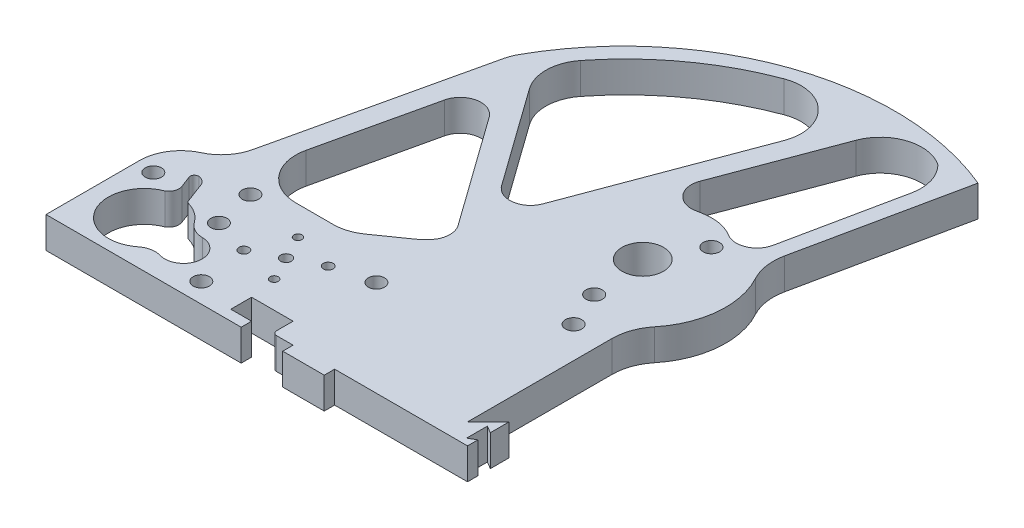
SolidWorks part; units mm, degrees
ref_plane "Front Plane" through (0, 0, 0) normal (0, 0, 1) x (1, 0, 0)
ref_plane "Top Plane" through (0, 0, 0) normal (0, 1, 0) x (1, 0, 0)
ref_plane "Right Plane" through (0, 0, 0) normal (1, 0, 0) x (0, 0, -1)
other "Bounding Box"
ref_plane "Default Plane" through (-8.9266, -12.7485, 0) normal (-0.1736, 0.9848, 0) x (0.9848, 0.1736, 0)
sketch "Sketch1" plane through (0, 0, 0) normal (0, 1, 0) x (1, 0, 0)
  line L0 (-19.2303, 19.05) -> (-2.5851, 30.7051)
  line L1 (-69.85, 19.05) -> (69.85, 19.05)
  line L2 (-69.85, 19.05) -> (-69.85, -19.05)
  line L3 (-69.85, -19.05) -> (69.85, -19.05)
  line L4 (69.85, 19.05) -> (69.85, -19.05)
  line L5 (-69.85, 19.05) -> (69.85, -19.05) construction
  line L6 (-69.85, -19.05) -> (69.85, 19.05) construction
  line L7 (-2.5851, 30.7051) -> (0.7868, 49.8283)
  line L8 (0.7868, 49.8283) -> (13.0319, 64.4214)
  line L9 (45.7626, 67.3847) -> (65.8767, 19.05)
  line L10 (47.1268, 73.5864) -> (45.7626, 67.3847)
  circle A0 centre (33.2658, 57.15) radius 6.35
  arc A1 (13.0319, 64.4214) -> (47.1268, 73.5864) centre (33.2658, 57.15) cw
  circle A2 centre (33.2658, 57.15) radius 76.2 construction
  point P0 (0, 0)
  dimension "D3" = 12.7
  dimension "D11" = 21.5008
  dimension "D17" = 152.4
  dimension "D6" = 38.1
  dimension "D8" = 36.5842
  dimension "D1" = 38.1
  dimension "D2" = 139.7
  dimension "D4" = 20.32
  dimension "D5" = 52.3528
  dimension "D7" = 6.35
  dimension "D9" = 19.05
  dimension "D10" = 19.4182
  dimension "D12" = 145
  dimension "D13" = 35
  dimension "D14" = 135
  dimension "D15" = 150
  dimension "D16" = 3.9733
extrude "Boss-Extrude1" add sketch "Sketch1" along normal blind 9.525 contours A1 L8 L7 L0 L1 L10 A0 | L4 L1 L2 L3 region at (0, 0, 0) region at (27.7925, 0, -42.2592)
sketch "Sketch2" plane through (0, 9.525, 0) normal (0, 1, 0) x (1, 0, 0)
  circle A0 centre (33.2658, 57.15) radius 76.2 construction
  dimension "D1" = 152.4
sketch "Sketch5" plane through (0, 9.525, 0) normal (0, 1, 0) x (1, 0, 0)
  line L0 (45.7626, 67.3847) -> (65.8767, 19.05) construction
  line L1 (69.85, -19.05) -> (49.53, -19.05)
  line L2 (69.85, -19.05) -> (69.85, 58.3315)
  line L3 (69.85, 58.3315) -> (49.53, 58.3315)
  line L4 (49.53, -19.05) -> (49.53, 58.3315)
  dimension "D1" = 20.32
extrude "Cut-Extrude4" cut sketch "Sketch5" against normal through all both and the other way through all
fillet "Fillet9" radius 12.7 1 edges at (-69.85, 4.7625, -19.05)
sketch "Sketch6" plane through (0, 9.525, 0) normal (0, 1, 0) x (1, 0, 0)
  line L1 (-57.15, 19.05) -> (-40.8203, 90.7577)
  line L2 (0.7868, 49.8283) -> (31.4279, 131.6561)
  line L3 (-50.6374, 19.05) -> (-36.1123, 82.8336)
  line L4 (-57.15, 19.05) -> (-19.2303, 19.05) construction
  line L5 (13.0319, 64.4214) -> (38.7682, 133.1511)
  line L6 (46.378, 65.9058) -> (58.1051, 122.2514)
  line L7 (-1.8369, 34.9484) -> (-0.1716, 44.3925)
  line L8 (45.7626, 67.3847) -> (49.53, 58.3315) construction
  line L9 (-57.15, 19.05) -> (-50.6374, 19.05)
  line L10 (0.7868, 49.8283) -> (13.0319, 64.4214)
  line L13 (-1.8369, 34.9484) -> (-36.1123, 82.8336)
  line L14 (-2.5851, 30.7051) -> (0.7868, 49.8283) construction
  line L15 (-1.8369, 34.9484) -> (0.7868, 49.8283)
  line L16 (-34.4703, 92.3103) -> (-0.1716, 44.3925)
  line L17 (-0.1716, 44.3925) -> (-1.8369, 34.9484)
  line L18 (46.378, 65.9058) -> (49.53, 58.3315)
  line L19 (49.53, 58.3315) -> (64.3361, 128.6003)
  circle A2 centre (33.2658, 57.15) radius 76.2 construction
  arc A4 (-40.8203, 90.7577) -> (64.3361, 128.6003) centre (32.4597, 52.1531) cw
  arc A5 (38.7682, 133.1511) -> (58.1051, 122.2514) centre (37.5674, 108.4182) cw
  arc A6 (-34.4703, 92.3103) -> (31.4279, 131.6561) centre (35.9864, 49.1637) cw
  line M10 (-19.2303, 19.05) -> (-57.15, 19.05)
  line M15 (49.53, 58.3315) -> (45.7626, 67.3847)
  line M18 (13.0319, 64.4214) -> (0.7868, 49.8283)
  dimension "D8" = 71.7077
  dimension "D12" = 82.6183
  dimension "D5" = 6.35
  dimension "D6" = 6.35
  dimension "D7" = 58.928
  dimension "D10" = 6.35
  dimension "D11" = 54.406
  dimension "D13" = 58.888
extrude "Boss-Extrude4" add sketch "Sketch6" against normal up to surface (9.525 mm away) contours L5 A5 L6 L1 L3 L13 L15 L16 L2 M15 M10 M18 region at (-47.3478, 9.525, -54.531) up to face at (-1.6293, 0, -32.9225)
sketch "Sketch4" plane through (0, 0, 0) normal (0, -1, 0) x (-1, 0, 0)
  line L1 (69.85, 6.35) -> (69.85, -19.05) construction
  line L5 (69.85, -19.05) -> (-49.53, -19.05) construction
  circle A0 centre (53.975, -8.0518) radius 10.9728
  dimension "D1" = 21.9456
  dimension "D2" = 15.875
  dimension "D3" = 10.9982
extrude "Cut-Extrude3" cut sketch "Sketch4" against normal through all both and the other way through all
fillet "Fillet13" radius 12.7 13 edges at (-57.15, 4.7625, -19.05) (-50.6374, 4.7625, -19.05) (-19.2303, 4.7625, -19.05) (-2.5851, 4.7625, -30.7051) (-0.1716, 4.7625, -44.3925) (-34.4703, 4.7625, -92.3103) (31.4279, 4.7625, -131.6561) (38.7682, 4.7625, -133.1511) (58.1051, 4.7625, -122.2514) (47.1268, 4.7625, -73.5864) (46.378, 4.7625, -65.9058) (-40.8203, 4.7625, -90.7577) (49.53, 4.7625, -58.3315)
fillet "Fillet14" radius 6.35 5 edges at (0.7868, 4.7625, -49.8283) (-1.8369, 4.7625, -34.9484) (-36.1123, 4.7625, -82.8336) (13.2325, 4.7625, -64.9569) (45.7626, 4.7625, -67.3847)
sketch "Sketch7" plane through (0, 0, 0) normal (0, -1, 0) x (-1, 0, 0)
  line L0 (69.85, -19.05) -> (-49.53, -19.05) construction
  line L1 (3.81, -19.05) -> (16.51, -19.05)
  line L2 (3.81, -19.05) -> (3.81, -12.7)
  line L3 (3.81, -12.7) -> (16.51, -12.7)
  line L4 (16.51, -19.05) -> (16.51, -12.7)
  line L5 (-49.53, 57.0081) -> (-49.53, -19.05) construction
  dimension "D1" = 53.34
  dimension "D2" = 12.7
  dimension "D3" = 6.35
extrude "Cut-Extrude5" cut sketch "Sketch7" against normal through all both and the other way through all
fillet "Fillet15" radius 1.27 1 edges at (-3.81, 4.7625, 19.05)
sketch "Sketch8" plane through (0, 9.525, 0) normal (0, 1, 0) x (1, 0, 0)
  line L1 (-69.85, -19.05) -> (-10.16, -19.05)
  line L2 (-69.85, -19.05) -> (-69.85, -22.225)
  line L3 (-69.85, -22.225) -> (-10.16, -22.225)
  line L4 (-10.16, -19.05) -> (-10.16, -22.225)
  line L5 (-2.54, -19.05) -> (49.53, -19.05) construction
  line L6 (2.54, -19.05) -> (15.24, -19.05)
  line L7 (2.54, -19.05) -> (2.54, -22.225)
  line L8 (2.54, -22.225) -> (15.24, -22.225)
  line L9 (15.24, -19.05) -> (15.24, -22.225)
  line L10 (-3.81, -12.7) -> (-3.81, -17.78) construction
  dimension "D1" = 3.175
  dimension "D2" = 59.69
  dimension "D3" = 12.7
  dimension "D4" = 6.35
  dimension "D5" = 3.175
extrude "Boss-Extrude5" add sketch "Sketch8" against normal up to surface (9.525 mm away) up to face at (-53.975, 0, 19.0246)
sketch "Sketch9" plane through (0, 0, 0) normal (0, -1, 0) x (1, 0, 0)
  line L0 (-69.85, -6.35) -> (-69.85, 22.225) construction
  line L2 (-10.16, 22.225) -> (-69.85, 22.225) construction
  circle A0 centre (-21.59, -2.921) radius 14.2875
  dimension "D1" = 28.575
  dimension "D2" = 48.26
  dimension "D3" = 25.146
extrude "Cut-Extrude6" cut sketch "Sketch9" against normal blind 5.08
sketch "Sketch10" plane through (0, 5.08, 0) normal (0, -1, 0) x (-1, 0, 0)
  circle A1 centre (21.59, 2.921) radius 1.651
  dimension "D1" = 3.302
extrude "Cut-Extrude7" cut sketch "Sketch10" against normal through all both and the other way through all
sketch "Sketch11" plane through (0, 9.525, 0) normal (0, 1, 0) x (1, 0, 0)
  line L0 (52.7216, 73.4788) -> (49.8029, 59.6266)
  line L1 (49.8029, 59.6266) -> (64.3361, 128.6003) construction
  line L2 (49.53, 57.0081) -> (49.53, 37.6401)
  line L3 (49.53, 57.0081) -> (49.53, -19.05) construction
  circle A0 centre (33.2658, 57.15) radius 25.4
  arc A2 (49.8029, 59.6266) -> (49.53, 57.0081) centre (62.23, 57.0081) ccw
  line M10 (49.53, -19.05) -> (49.53, 57.0081)
  arc M11 (49.53, 57.0081) -> (49.8029, 59.6266) centre (62.23, 57.0081) cw
  line M12 (49.8029, 59.6266) -> (64.3361, 128.6003)
  dimension "D1" = 50.8
extrude "Boss-Extrude6" add sketch "Sketch11" against normal up to surface (9.525 mm away) contours A0 M10 M12 M11 region at (53.6069, 9.525, -55.4705) up to face at (-21.59, 0, -17.2085)
fillet "Fillet16" radius 15.24 2 edges at (49.53, 4.7625, -37.6401) (52.7216, 4.7625, -73.4788)
sketch "Sketch12" plane through (0, 5.08, 0) normal (0, -1, 0) x (1, 0, 0)
  line L3 (-17.873, -20.2372) -> (-17.873, 22.225) construction
  line L5 (-10.16, 22.225) -> (-69.85, 22.225) construction
  line L6 (-16.51, 12.7) -> (-16.51, 19.05) construction
  circle A0 centre (-21.59, -2.921) radius 1.651 construction
  circle A1 centre (-25.307, -10.2862) radius 1.25
  circle A2 centre (-30.1605, 1.4042) radius 1.5
  circle A3 centre (-17.873, 4.4442) radius 1.25
  circle A4 centre (-13.0195, -7.2462) radius 1.5
  arc A5 (-15.9502, -21.3468) -> (-23.2346, -19.05) centre (-23.2346, -31.75) ccw construction
  circle B0 centre (-13.0195, -7.2462) radius 1.5
  circle B1 centre (-25.307, -10.2862) radius 1.25
  circle B2 centre (-30.1605, 1.4042) radius 1.5
  circle B3 centre (-17.873, 4.4442) radius 1.25
  circle B4 centre (-21.59, -2.921) radius 4
  circle B5 centre (-21.59, -2.921) radius 13.925
  dimension "D1" = 1.363
sketch_block_instance "Wepon motor-1"
sketch_block "Wepon motor" parameters "D1"=27.85, "D2"=3, "D3"=2.5, "D4"=8
extrude "Cut-Extrude8" cut sketch "Sketch12" against normal up to surface (4.445 mm away) contours A4 | A1 | A2 | B3 | A3 | A3 region at (-25.307, 5.08, -10.2862) region at (-30.1605, 5.08, 1.4042) region at (-17.873, 5.08, 4.4442) region at (-13.0195, 5.08, -7.2462) up to face at (-2.0065, 9.525, -15.4705)
sketch "Sketch13" plane through (0, 0, 0) normal (0, -1, 0) x (-1, 0, 0)
  line L0 (10.16, -22.225) -> (69.85, -22.225) construction
  line L1 (69.85, 6.35) -> (69.85, -22.225) construction
  line L2 (51.6741, 3.1427) -> (53.9746, 9.2296)
  line L3 (57.857, 9.5431) -> (56.5388, 6.0555)
  line L4 (50.856, 2.3768) -> (58.2843, 2.0037)
  circle A2 centre (28.3994, -16.1925) radius 2.4892
  circle A3 centre (41.1691, 1.9672) radius 2.4892
  circle A4 centre (64.5668, 5.3086) radius 2.4892
  arc A7 (39.9498, -4.4075) -> (41.5187, -15.6078) centre (39.915, -10.1224) ccw
  arc A8 (39.915, -4.4074) -> (45.1206, -1.7461) centre (39.9518, 1.9426) ccw
  arc A9 (41.5187, -15.6078) -> (47.2419, -16.7237) centre (43.3006, -21.7026) cw
  circle A11 centre (39.915, -10.1224) radius 5.715
  arc A12 (39.915, -4.4074) -> (44.5381, -2.4494) centre (39.9518, 1.9426) ccw
  arc A13 (41.5187, -15.6078) -> (46.487, -16.2099) centre (43.3006, -21.7026) cw
  arc A14 (50.856, 2.3768) -> (51.6741, 3.1427) centre (50.4861, 3.5917) ccw
  arc A15 (53.9746, 9.2296) -> (56.4853, 11.2488) centre (56.9445, 8.1072) cw
  arc A16 (56.4853, 11.2488) -> (57.857, 9.5431) centre (56.669, 9.9921) cw
  arc A17 (56.5388, 6.0555) -> (58.2843, 2.0037) centre (59.5088, 4.933) ccw
  line B0 (51.6741, 3.1427) -> (53.9746, 9.2296)
  line B1 (56.5388, 6.0555) -> (57.857, 9.5431)
  line B2 (59.1668, 11.9371) -> (56.2623, 14.2113)
  line B3 (54.2914, 13.6603) -> (53.2994, 11.0355)
  circle B4 centre (28.3994, -16.1925) radius 4.7625
  circle B5 centre (41.1691, 1.9672) radius 4.7625
  circle B6 centre (64.5668, 5.3086) radius 4.7625
  arc B7 (47.2419, -16.7237) -> (58.2843, 2.0037) centre (54.0523, -8.1202) ccw
  arc B8 (39.9325, -4.4074) -> (41.5187, -15.6078) centre (39.915, -10.1224) ccw
  arc B9 (47.2419, -16.7237) -> (41.5187, -15.6078) centre (43.3006, -21.7026) ccw
  arc B10 (45.1206, -1.7461) -> (39.9325, -4.4074) centre (39.9519, 1.9426) cw
  arc B11 (50.856, 2.3768) -> (51.6741, 3.1427) centre (50.4861, 3.5917) ccw
  arc B12 (56.5388, 6.0555) -> (58.2843, 2.0037) centre (59.5088, 4.933) ccw
  arc B13 (53.9746, 9.2296) -> (56.4853, 11.2488) centre (56.9445, 8.1072) cw
  arc B14 (56.4853, 11.2488) -> (57.857, 9.5431) centre (56.669, 9.9921) cw
  arc B15 (50.856, 2.3768) -> (45.1206, -1.7461) centre (54.0523, -8.1202) ccw
  arc B16 (26.9014, -10.349) -> (33.1492, -19.9115) centre (28.3994, -16.1925) ccw
  arc B17 (33.1492, -19.9115) -> (37.2652, -17.8006) centre (37.1178, -22.5816) cw
  arc B18 (37.2652, -17.8006) -> (41.9338, -17.0647) centre (37.6565, -5.1066) ccw
  arc B19 (41.9338, -17.0647) -> (47.18, -18.4806) centre (43.5377, -21.549) cw
  arc B20 (49.0637, -20.2979) -> (47.18, -18.4806) centre (56.8928, -10.2982) cw
  arc B21 (49.0637, -20.2979) -> (64.2612, -17.915) centre (55.097, -9.1225) ccw
  arc B22 (64.2612, -17.915) -> (66.7679, -1.9177) centre (54.0523, -8.1202) ccw
  arc B23 (66.7679, -1.9177) -> (68.5811, 1.6191) centre (56.5124, 5.5732) ccw
  arc B24 (68.5811, 1.6191) -> (68.9549, 2.3892) centre (71.5983, 0.6305) cw
  arc B25 (68.9549, 2.3892) -> (61.6247, 9.6815) centre (64.5668, 5.3086) ccw
  arc B26 (61.6247, 9.6815) -> (59.6498, 10.8362) centre (60.9158, 10.7352) cw
  arc B27 (59.6498, 10.8362) -> (59.1668, 11.9371) centre (58.3838, 10.9372) ccw
  arc B28 (56.2623, 14.2113) -> (54.2914, 13.6603) centre (55.4794, 13.2113) ccw
  arc B29 (53.2994, 11.0355) -> (51.0076, 9.0562) centre (50.3294, 12.158) cw
  arc B30 (51.0076, 9.0562) -> (45.8856, 7.0672) centre (54.8054, -8.3134) ccw
  arc B31 (45.8856, 7.0672) -> (43.1184, 6.8639) centre (44.2927, 9.8138) cw
  arc B32 (43.1184, 6.8639) -> (36.0999, 0.5245) centre (41.1691, 1.9672) ccw
  arc B33 (36.0999, 0.5245) -> (34.7175, -5.456) centre (29.9924, -1.2137) cw
  arc B34 (26.9014, -10.349) -> (30.8214, -8.5944) centre (23.7477, 1.9532) ccw
  arc B35 (30.8214, -8.5944) -> (34.7175, -5.456) centre (14.8524, 15.217) ccw
  dimension "D3" = 4.9784
  dimension "D1" = 27.5336
  dimension "D2" = 5.2832
sketch_block_instance "Wire cover-1"
sketch_block "Wire cover"
extrude "Cut-Extrude10" cut sketch "Sketch13" against normal through all both and the other way through all contours L4 A17 L3 A16 A15 L2 A14 | A4 | A3 | A11 | A2
fillet "Fillet18" radius 6.35 2 edges at (-43.299, 4.7625, 5.517) (-44.483, 4.7625, 13.5567)
sketch "Sketch14" plane through (0, 0, 0) normal (0, -1, 0) x (-1, 0, 0)
  line B0 (-64.3361, 128.6003) -> (-54.0401, 79.736)
  line B1 (-49.53, 31.4772) -> (-49.53, -19.05)
  line B2 (-49.53, -19.05) -> (-15.24, -19.05)
  line B3 (-15.24, -19.05) -> (-15.24, -22.225)
  line B4 (-15.24, -22.225) -> (-2.54, -22.225)
  line B5 (-2.54, -22.225) -> (-2.54, -19.05)
  line B6 (-2.54, -19.05) -> (2.54, -19.05)
  line B7 (3.81, -17.78) -> (3.81, -12.7)
  line B8 (3.81, -12.7) -> (16.51, -12.7)
  line B9 (16.51, -12.7) -> (16.51, -19.05)
  line B10 (16.51, -19.05) -> (10.16, -19.05)
  line B11 (10.16, -19.05) -> (10.16, -22.225)
  line B12 (10.16, -22.225) -> (69.85, -22.225)
  line B13 (69.85, -22.225) -> (69.85, 6.35)
  line B14 (55.4349, 26.5812) -> (41.206, 89.0639)
  arc B15 (-54.0401, 79.736) -> (-55.5701, 69.3024) centre (-68.9526, 76.5938) cw
  arc B16 (-55.5701, 69.3024) -> (-52.9559, 41.1045) centre (-33.2658, 57.15) ccw
  arc B17 (-52.9559, 41.1045) -> (-49.53, 31.4772) centre (-64.77, 31.4772) cw
  arc B18 (3.81, -17.78) -> (2.54, -19.05) centre (2.54, -17.78) cw
  arc B19 (39.9214, 92.4179) -> (-64.3361, 128.6003) centre (-32.4597, 52.1531) ccw
  arc B20 (39.9214, 92.4179) -> (41.206, 89.0639) centre (28.8231, 86.244) cw
  arc B21 (55.4349, 26.5812) -> (62.484, 17.8756) centre (67.8179, 29.4011) ccw
  arc B22 (62.484, 17.8756) -> (69.85, 6.35) centre (57.15, 6.35) cw
sketch_block_instance "Block1-1"
sketch_block "Block1"
sketch "Sketch15" plane through (0, 9.525, 0) normal (0, 1, 0) x (1, 0, 0)
  line L2 (15.24, -19.05) -> (49.53, -19.05) construction
  line L3 (-69.85, 6.35) -> (-69.85, -22.225) construction
  circle A2 centre (40.5384, 70.866) radius 2.5
  circle A3 centre (35.179, 40.386) radius 2.5
  circle A4 centre (39.9034, 29.3624) radius 2.5
  dimension "D1" = 5
  dimension "D4" = 5
  dimension "D7" = 5
  dimension "D2" = 89.916
  dimension "D3" = 110.3884
  dimension "D5" = 59.436
  dimension "D6" = 105.029
  dimension "D8" = 48.4124
  dimension "D9" = 109.7534
extrude "Cut-Extrude11" cut sketch "Sketch15" against normal through all both and the other way through all
sketch "Sketch16" plane through (0, 9.525, 0) normal (0, 1, 0) x (1, 0, 0)
  line L0 (49.53, -12.7) -> (55.88, -6.35)
  line L1 (49.53, 31.4772) -> (49.53, -19.05) construction
  line L2 (55.88, -6.35) -> (55.88, -19.05)
  line L3 (55.88, -19.05) -> (49.53, -19.05)
  line L4 (49.53, -12.7) -> (49.53, -19.05)
  line L5 (55.88, -12.065) -> (53.6803, -10.795)
  line L6 (53.6803, -10.795) -> (53.6803, -17.145)
  line L7 (53.6803, -17.145) -> (55.88, -15.875)
  dimension "D1" = 6.35
  dimension "D2" = 6.35
  dimension "D3" = 12.7
  dimension "D4" = 3.175
  dimension "D5" = 3.81
  dimension "D6" = 6.35
  dimension "D7" = 2.54
  dimension "D8" = 2.54
extrude "Boss-Extrude7" add sketch "Sketch16" against normal up to surface (9.525 mm away) contours L7 L6 L5 L2 L0 L4 L3 region at (52.6882, 9.525, 14.1431) up to face at (40.5384, 0, -68.366)
sketch "Sketch18" plane through (0, 9.525, 0) normal (0, 1, 0) x (1, 0, 0)
  line B0 (49.53, -12.7) -> (49.53, -19.05)
  line B1 (49.53, -19.05) -> (55.88, -19.05)
  line B2 (55.88, -19.05) -> (55.88, -15.875)
  line B3 (55.88, -15.875) -> (53.6803, -17.145)
  line B4 (53.6803, -17.145) -> (53.6803, -10.795)
  line B5 (53.6803, -10.795) -> (55.88, -12.065)
  line B6 (55.88, -12.065) -> (55.88, -6.35)
  line B7 (55.88, -6.35) -> (49.53, -12.7)
sketch_block_instance "Block3-1"
sketch_block "Block3"
sketch "Sketch19" plane through (0, 9.525, 0) normal (0, 1, 0) x (-1, 0, 0)
  line L0 (69.85, -6.35) -> (69.85, 22.225) construction
  line L2 (69.85, 22.225) -> (10.16, 22.225) construction
  circle A0 centre (43.8658, -14.3002) radius 2.4892
  circle A3 centre (1.3208, -10.287) radius 2.4892
  dimension "D1" = 4.9784
  dimension "D2" = 25.9842
  dimension "D3" = 36.5252
  dimension "D4" = 32.512
  dimension "D5" = 68.5292
extrude "Cut-Extrude12" cut sketch "Sketch19" against normal through all both and the other way through all
